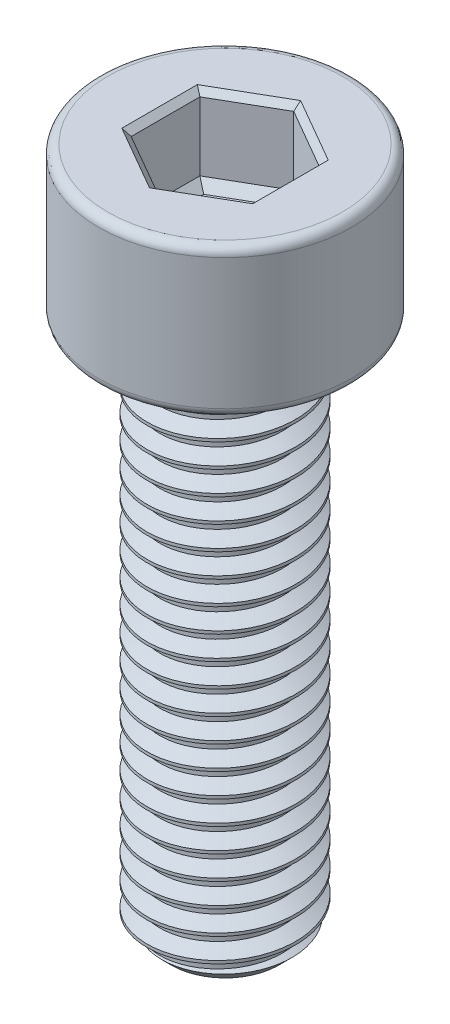
SolidWorks part; units mm, degrees
material "AISI Type A2 Tool Steel"
ref_plane "Front Plane" through (0, 0, 0) normal (0, 0, 1) x (1, 0, 0)
ref_plane "Top Plane" through (0, 0, 0) normal (0, 1, 0) x (1, 0, 0)
ref_plane "Right Plane" through (0, 0, 0) normal (1, 0, 0) x (0, 0, -1)
sketch "Sketch1" plane through (0, 0, 0) normal (0, 1, 0) x (1, 0, 0)
  circle A0 centre (0, 0) radius 2.5
  dimension "D1" = 5
extrude "Boss-Extrude1" add sketch "Sketch1" along normal blind 18
thread "Thread1" pitch 0.8 method cut profile "Thread Profile1" start angle 0, offset 1, length 0, pitch 0.8, diameter 5
ref_plane "Plane1" through (-2.5, 19, 0) normal (0, 0, 1) x (-1, 0, 0)
sketch "Thread Profile1" plane through (-2.5, 19, 0) normal (0, 0, 1) x (-1, 0, 0)
  line L0 (0, 0) -> (0, 0.8) construction
  line L11 (0, 0) -> (0, 0.7)
  line L12 (0, 0.7) -> (-0.433, 0.45)
  line L13 (-0.433, 0.45) -> (-0.433, 0.25)
  line L15 (-0.433, 0.25) -> (0, 0)
  line L17 (-0.433, 0.35) -> (0, 0.35) construction
  point P2 (0, 0)
  dimension "Pitch" = 0.8
  dimension "Profile_Angle" = 60
  dimension "Profile_Land" = 0.2
  dimension "Profile_Height" = 0.433
sketch "Sketch5" plane through (0, 18, 0) normal (0, 1, 0) x (1, 0, 0)
  circle A0 centre (0, 0) radius 4.25
  dimension "D1" = 8.5
extrude "Boss-Extrude2" add sketch "Sketch5" along normal blind 5
fillet "Fillet1" radius 0.3 2 edges at (0, 18, 4.25) (0, 23, 4.25)
sketch "Sketch6" plane through (0, 0, 0) normal (0, 0, 1) x (1, 0, 0)
  line L0 (0, 0) -> (0, 0.2882) construction
  line L1 (0, 0) -> (2.51, 0) construction
  line L2 (2.51, 0) -> (2.51, 0.7)
  line L3 (2.51, 0.7) -> (1.81, 0)
  line L4 (1.81, 0) -> (2.51, 0)
  dimension "D1" = 45
  dimension "D2" = 0.7
  dimension "D3" = 2.51
revolve "Cut-Revolve1" cut sketch "Sketch6" angle 360 about L0
sketch "Sketch7" plane through (0, 23, 0) normal (0, 1, 0) x (1, 0, 0)
  line L1 (0, 2.3094) -> (-2, 1.1547)
  line L2 (-2, 1.1547) -> (-2, -1.1547)
  line L3 (-2, -1.1547) -> (0, -2.3094)
  line L4 (0, -2.3094) -> (2, -1.1547)
  line L5 (2, -1.1547) -> (2, 1.1547)
  line L6 (2, 1.1547) -> (0, 2.3094)
  circle A0 centre (0, 0) radius 2 construction
  dimension "D1" = 4
extrude "Cut-Extrude1" cut sketch "Sketch7" against normal blind 2.5
chamfer "Chamfer1" distance 0.2 angle 45 6 edges at (-2, 23, 0) (-1, 23, 1.7321) (1, 23, 1.7321) (2, 23, 0) (1, 23, -1.7321) (-1, 23, -1.7321)
sketch "Sketch8" plane through (0, 20.5, 0) normal (0, 1, 0) x (1, 0, 0)
  line L1 (0, 2.3094) -> (-2, 1.1547)
  line L2 (-2, 1.1547) -> (-2, -1.1547)
  line L3 (-2, -1.1547) -> (0, -2.3094)
  line L4 (0, -2.3094) -> (2, -1.1547)
  line L5 (2, -1.1547) -> (2, 1.1547)
  line L6 (2, 1.1547) -> (0, 2.3094)
  circle A0 centre (0, 0) radius 2 construction
extrude "Cut-Extrude2" cut sketch "Sketch8" against normal blind 0.3 draft 45
